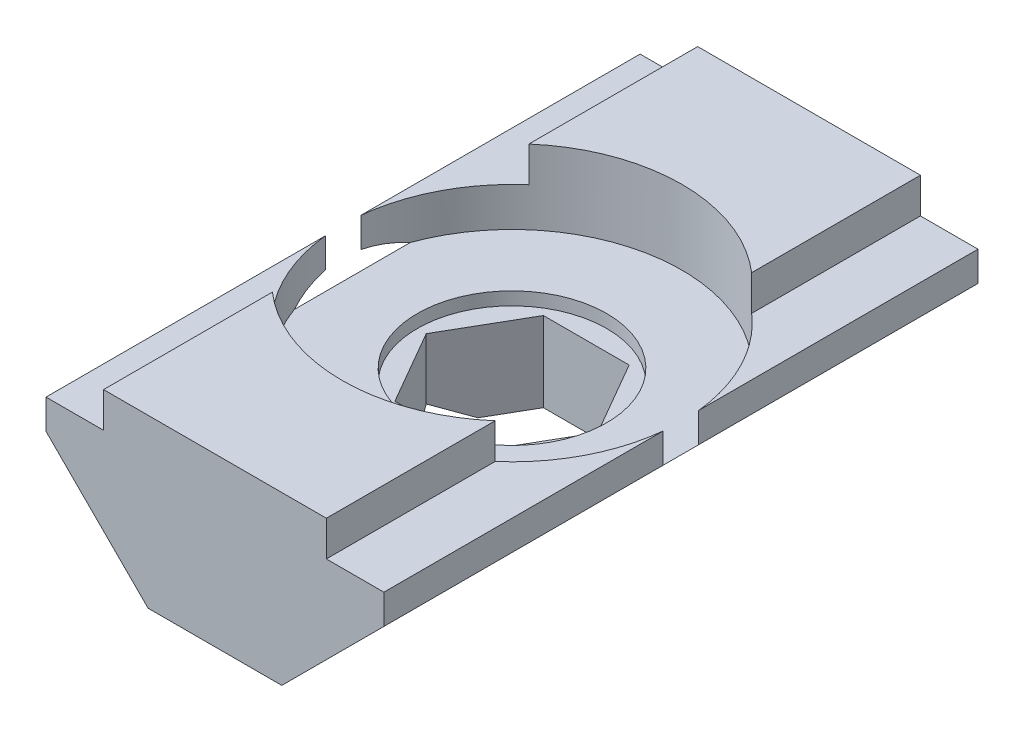
SolidWorks part; units mm, degrees
ref_plane "Front Plane" through (0, 0, 0) normal (0, 0, 1) x (1, 0, 0)
ref_plane "Top Plane" through (0, 0, 0) normal (0, 1, 0) x (1, 0, 0)
ref_plane "Right Plane" through (0, 0, 0) normal (1, 0, 0) x (0, 0, -1)
sketch "Sketch1" plane through (0, 0, 0) normal (0, 0, 1) x (1, 0, 0)
  line L0 (0, 0) -> (0, 5972.9771) construction
  line L1 (0, 0) -> (-5972.9771, 0) construction
  line L2 (0, 0) -> (0, 0.95)
  line L3 (0, 0.95) -> (6, 0.95)
  line L4 (6, 0.95) -> (6, 0)
  line L5 (6, 0) -> (7.55, 0)
  line L6 (7.55, 0) -> (7.55, -0.8)
  line L7 (7.55, -0.8) -> (4.8, -3.55)
  line L8 (4.8, -3.55) -> (1.2, -3.55)
  line L9 (1.2, -3.55) -> (-1.55, -0.8)
  line L10 (-1.55, -0.8) -> (-1.55, 0)
  line L11 (-1.55, 0) -> (0, 0)
  dimension "D1" = 0.95
  dimension "D2" = 1.55
  dimension "D3" = 1.55
  dimension "D4" = 6
  dimension "D5" = 0.8
  dimension "D6" = 0.8
  dimension "D7" = 135
  dimension "D8" = 135
  dimension "D9" = 4.5
extrude "Boss-Extrude1" add sketch "Sketch1" along normal blind 16
sketch "Sketch2" plane through (0, 0.95, 0) normal (0, 1, 0) x (1, 0, 0)
  line L0 (0, -8) -> (6, -8) construction
  line L1 (0, -16) -> (0, 0) construction
  line L2 (6, -16) -> (6, 0) construction
  circle A0 centre (3, -8) radius 4.575
  dimension "D1" = 9.15
extrude "Cut-Extrude1" cut sketch "Sketch2" against normal blind 2
sketch "Sketch3" plane through (0, -1.05, 0) normal (0, 1, 0) x (1, 0, 0)
  line L0 (3, -8) -> (5.3094, -8) construction
  line L1 (5.3094, -8) -> (4.1547, -6)
  line L2 (4.1547, -6) -> (1.8453, -6)
  line L3 (1.8453, -6) -> (0.6906, -8)
  line L4 (0.6906, -8) -> (1.8453, -10)
  line L5 (1.8453, -10) -> (4.1547, -10)
  line L6 (4.1547, -10) -> (5.3094, -8)
  circle A0 centre (3, -8) radius 2 construction
  dimension "D1" = 4
extrude "Cut-Extrude2" cut sketch "Sketch3" against normal through all
sketch "Sketch4" plane through (0, -1.05, 0) normal (0, 1, 0) x (1, 0, 0)
  circle A0 centre (3, -8) radius 2.55
  dimension "D1" = 5.1
extrude "Cut-Extrude3" cut sketch "Sketch4" against normal blind 0.35
